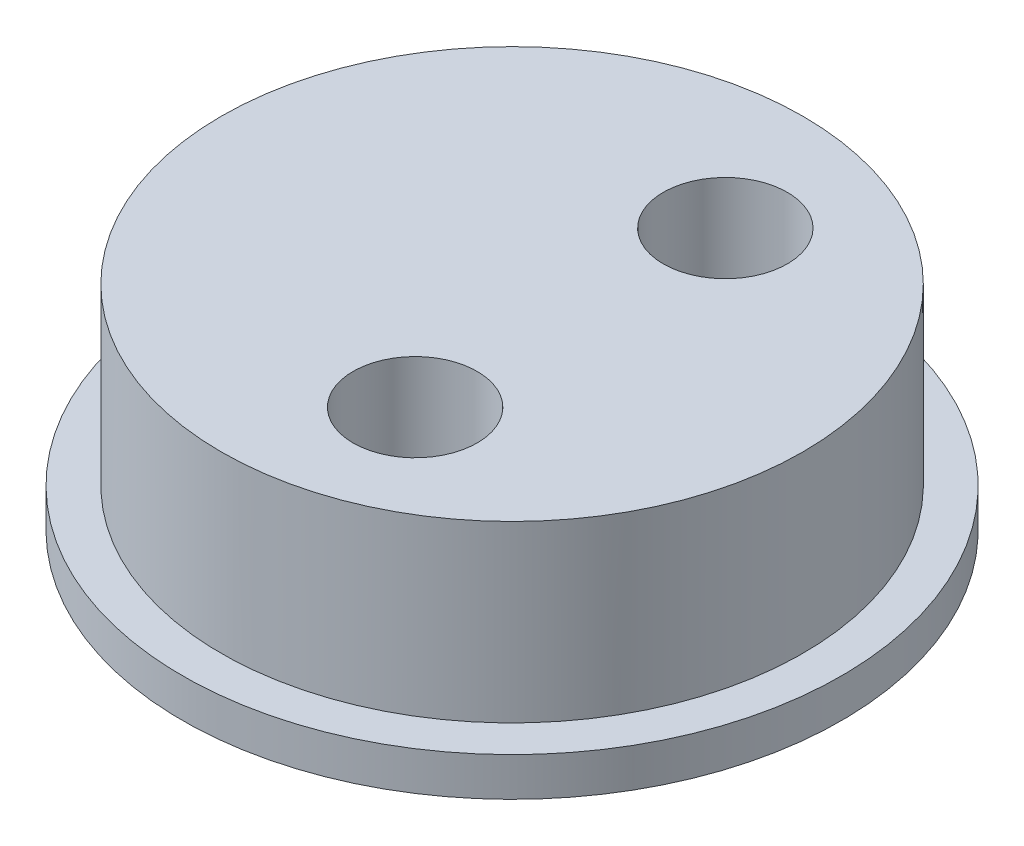
SolidWorks part; units mm, degrees
ref_plane "Front Plane" through (0, 0, 0) normal (0, 0, 1) x (1, 0, 0)
ref_plane "Top Plane" through (0, 0, 0) normal (0, 1, 0) x (1, 0, 0)
ref_plane "Right Plane" through (0, 0, 0) normal (1, 0, 0) x (0, 0, -1)
sketch "Sketch1" plane through (0, 0, 0) normal (0, 1, 0) x (1, 0, 0)
  line L0 (0, 0) -> (-1.5, 0) construction
  circle A1 centre (-1.5, 0) radius 7.5
  point P12 (0, 0)
  dimension "D3" = 15
  dimension "D2" = 1.5
extrude "Boss-Extrude1" add sketch "Sketch1" along normal blind 5.5
sketch "Sketch2" plane through (0, 0, 0) normal (0, -1, 0) x (1, 0, 0)
  line L0 (-12.8187, 0) -> (7.6603, 0) construction
  circle A0 centre (-1.5, 0) radius 8.5
  dimension "D2" = 17
  dimension "D1" = 1.5
extrude "Boss-Extrude2" add sketch "Sketch2" against normal blind 1
sketch "Sketch4" plane through (0, 5.5, 0) normal (0, 1, 0) x (1, 0, 0)
  line L0 (0, 8.8969) -> (0, -8.7328) construction
  circle A0 centre (0, 0) radius 4 construction
  circle A1 centre (0, 4) radius 1.6
  circle A2 centre (0, -4) radius 1.6
  dimension "D1" = 8
  dimension "D2" = 3.2
extrude "Cut-Extrude1" cut sketch "Sketch4" against normal through all
